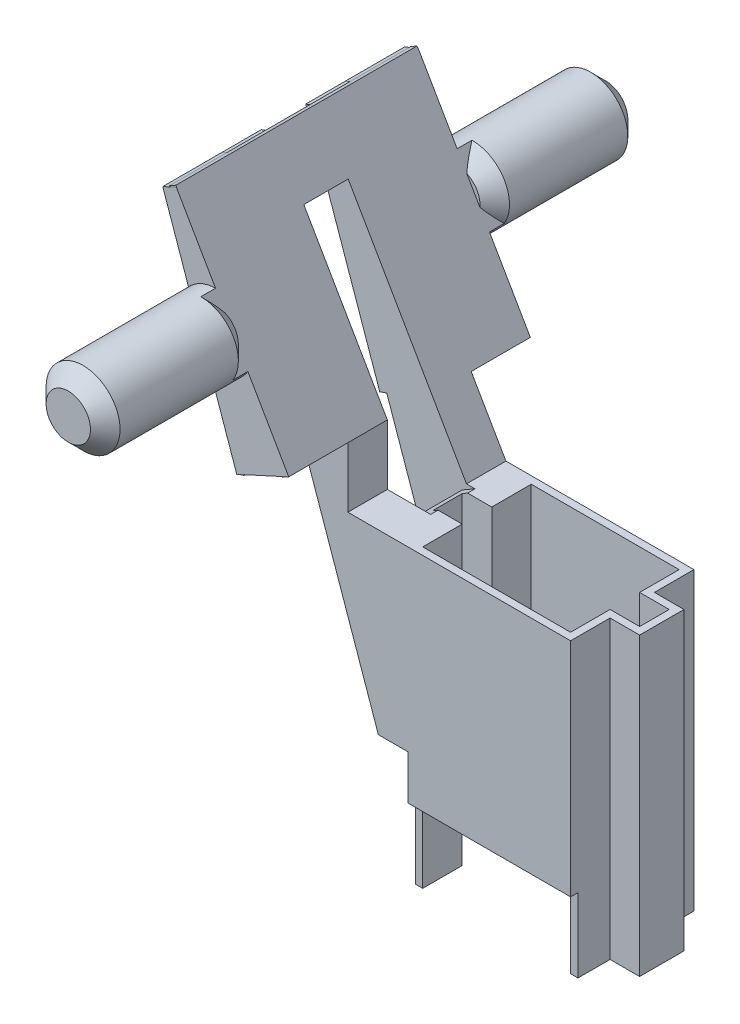
SolidWorks part; units mm, degrees
ref_plane "Ebene vorne" through (0, 0, 0) normal (0, 0, 1) x (1, 0, 0)
ref_plane "Ebene oben" through (0, 0, 0) normal (0, 1, 0) x (1, 0, 0)
ref_plane "Ebene rechts" through (0, 0, 0) normal (1, 0, 0) x (0, 0, -1)
sketch "Skizze1" plane through (0, 0, 0) normal (0, 1, 0) x (1, 0, 0)
  line L0 (-5, 1) -> (-5, 3.67)
  line L1 (5, -3.67) -> (-5, -3.67)
  line L2 (5, -3.67) -> (5, -1)
  line L3 (5, 3.67) -> (-5, 3.67)
  line L4 (-5, -3.67) -> (-5, -1)
  line L5 (5, -3.67) -> (-5, 3.67) construction
  line L6 (5, 3.67) -> (-5, -3.67) construction
  line L7 (7, -1) -> (5, -1)
  line L8 (7, -1) -> (7, 1)
  line L9 (7, 1) -> (5, 1)
  line L10 (-7, -1) -> (-7, 1)
  line L11 (7, -1) -> (-7, 1) construction
  line L12 (7, 1) -> (-7, -1) construction
  line L13 (5.5, -4.17) -> (-5.5, -4.17)
  line L14 (7.5, -1.5) -> (7.5, 1.5)
  line L15 (5.5, 4.17) -> (-5.5, 4.17)
  line L16 (-7.5, -1.5) -> (-7.5, 1.5)
  line L17 (5.5, -2.87) -> (-5.5, 2.87) construction
  line L18 (5.5, 3.21) -> (-5.5, -3.21) construction
  line L19 (-5, 1) -> (-7, 1)
  line L20 (5, 1) -> (5, 3.67)
  line L21 (-5, -1) -> (-7, -1)
  line L25 (-7.5, 1.5) -> (-5.5, 1.5)
  line L26 (-5.5, 4.17) -> (-5.5, 1.5)
  line L29 (7.5, 1.5) -> (5.5, 1.5)
  line L30 (5.5, 4.17) -> (5.5, 1.5)
  line L33 (7.5, -1.5) -> (5.5, -1.5)
  line L34 (5.5, -4.17) -> (5.5, -1.5)
  line L37 (-7.5, -1.5) -> (-5.5, -1.5)
  line L38 (-5.5, -4.17) -> (-5.5, -1.5)
  point P0 (0, 0)
  point P5 (0, 0)
  point P11 (0, 0)
  dimension "D1" = 10
  dimension "D2" = 2
  dimension "D3" = 14
  dimension "D4" = 0.5
  dimension "D5" = 0.5
  dimension "D6" = 7.34
  dimension "D7" = 0.5
  dimension "D8" = 0.5
  dimension "D9" = 0.5
  dimension "D10" = 0.5
  dimension "D11" = 0.5
  dimension "D12" = 0.5
extrude "Aufsatz-Linear austragen1" add sketch "Skizze1" along normal blind 20
sketch "Skizze8" plane through (0, 0, 3.67) normal (0, 0, -1) x (-1, 0, 0)
  line L0 (5.5, 20) -> (5.5, 0) construction
  line L1 (-5.5, 0) -> (5.5, 0)
  line L2 (-5.5, 0) -> (-5.5, 5)
  line L3 (-5.5, 5) -> (5.5, 5)
  line L4 (5.5, 0) -> (5.5, 5)
  dimension "D1" = 5
extrude "Schnitt-Linear austragen2" cut sketch "Skizze8" against normal up to next
sketch "Skizze10" plane through (0, 0, -4.17) normal (0, 0, -1) x (-1, 0, 0)
  line L1 (5.5, 20) -> (7.2113, 20)
  line L2 (5.5, 20) -> (5.5, 19.5)
  line L3 (5.5, 19.5) -> (7.5, 19.5)
  line L5 (7.5, 19.5) -> (17.6443, 37.0705)
  line L6 (17.6443, 37.0705) -> (17.2113, 37.3205)
  line L7 (17.2113, 37.3205) -> (7.2113, 20)
  line L8 (7.5, 20) -> (7.5, 0) construction
  dimension "D1" = 0.5
  dimension "D2" = 0.5
  dimension "D3" = 150
  dimension "D4" = 20
extrude "Aufsatz-Linear austragen3" add sketch "Skizze10" against normal up to vertex (8.34 mm away) up to point (-5.5, 20, 4.17)
sketch "Skizze12" plane through (0, 19.5, 0) normal (0, -1, 0) x (1, 0, 0)
  line L1 (-7, -1) -> (-5.5, -1)
  line L2 (-7, -1) -> (-7, 1)
  line L3 (-7, 1) -> (-5.5, 1)
  line L4 (-5.5, -1) -> (-5.5, 1)
extrude "Schnitt-Linear austragen3" cut sketch "Skizze12" against normal up to next
sketch "Skizze13" plane through (0, 0, -4.17) normal (0, 0, -1) x (-1, 0, 0)
  line L0 (17.2113, 37.3205) -> (9.5613, 24.0703)
  line L1 (17.2113, 37.3205) -> (7.2113, 20) construction
  line L2 (9.5613, 24.0703) -> (9.9943, 23.8203)
  line L3 (7.5, 19.5) -> (17.6443, 37.0705) construction
  line L4 (9.9943, 23.8203) -> (17.6443, 37.0705)
  line L5 (17.6443, 37.0705) -> (17.2113, 37.3205)
  dimension "D1" = 15.3
extrude "Aufsatz-Linear austragen4" add sketch "Skizze13" along normal blind 3.98
sketch "Skizze15" plane through (0, 0, -1.5) normal (0, 0, -1) x (-1, 0, 0)
  line L4 (5.5, 8) -> (5.5, 19.5)
  line L5 (5.5, 19.5) -> (7.5, 19.5)
  line L6 (7.5, 19.5) -> (17.6443, 37.0705)
  line L14 (17.6443, 37.0705) -> (7.5, 8)
  line L15 (7.5, 19.5) -> (7.5, 0) construction
  line L16 (7.5, 8) -> (5.5, 8)
  line L17 (5.5, 0) -> (7.5, 0) construction
  dimension "D1" = 8
extrude "Aufsatz-Linear austragen5" add sketch "Skizze15" along normal up to vertex (2.67 mm away) up to point (-7.5, 19.5, -4.17)
mirror "Spiegeln1" about plane through (0, 0, 0) normal (0, 0, 1) of "Aufsatz-Linear austragen4"
sketch "Skizze16" plane through (0, 0, 1.5) normal (0, 0, 1) x (1, 0, 0)
  line L0 (-17.6443, 37.0705) -> (-7.5, 8)
  line L1 (-7.5, 8) -> (-5.5, 8)
  line L2 (-5.5, 19.5) -> (-5.5, 5) construction
  line L3 (-5.5, 8) -> (-5.5, 19.5)
  line L4 (-5.5, 19.5) -> (-7.5, 19.5)
  line L5 (-7.5, 19.5) -> (-17.6443, 37.0705)
extrude "Aufsatz-Linear austragen6" add sketch "Skizze16" along normal up to vertex (2.67 mm away) up to point (-7.5, 19.5, 4.17)
sketch "Skizze17" plane through (2.8187, 1.6274, 0) normal (-0.866, -0.5, 0) x (0, 0, 1)
  line L0 (1.5, 40.9262) -> (1.5, 10.6782) construction
  line L1 (-1.5, 20.6375) -> (1.5, 20.6375)
  line L2 (-1.5, 20.6375) -> (-1.5, 36.9262)
  line L3 (-1.5, 36.9262) -> (1.5, 36.9262)
  line L4 (1.5, 20.6375) -> (1.5, 36.9262)
  line L6 (1.5, 40.9262) -> (-1.5, 40.9262) construction
  dimension "D1" = 4
extrude "Schnitt-Linear austragen4" cut sketch "Skizze17" against normal up to next
sketch "Skizze22" plane through (0, 0, -1.5) normal (0, 0, 1) x (1, 0, 0)
  line L0 (-17.6114, 36.9761) -> (-12.6034, 22.6248)
  line L1 (-17.6443, 37.0705) -> (-7.5, 8) construction
  line L2 (-12.6034, 22.6248) -> (-13.0755, 22.46)
  line L3 (-13.0755, 22.46) -> (-18.0835, 36.8114)
  line L4 (-18.0835, 36.8114) -> (-17.6114, 36.9761)
  dimension "D1" = 15.2
  dimension "D2" = 0.5
  dimension "D3" = 0.1
extrude "Aufsatz-Linear austragen15" add sketch "Skizze22" against normal blind 6.65
mirror "Spiegeln2" about plane through (0, 0, 0) normal (0, 0, 1) of "Aufsatz-Linear austragen15"
sketch "Skizze23" plane through (0, 0, 4.17) normal (0, 0, 1) x (1, 0, 0)
  line L0 (-7.2113, 20) -> (-9.5613, 20)
  line L1 (-9.5613, 20) -> (-9.5613, 24.0703)
  line L3 (-7.2113, 20) -> (-9.5613, 24.0703)
  line L4 (-9.5613, 24.0703) -> (-7.2113, 20) construction
extrude "Schnitt-Linear austragen5" cut sketch "Skizze23" against normal up to next
sketch "Skizze24" plane through (0, 0, 4.17) normal (0, 0, 1) x (1, 0, 0)
  line L2 (-17.6443, 37.0705) -> (-11.2989, 23.2225) construction
  line L3 (-18.0835, 36.8114) -> (-17.1613, 37.2339)
  line L4 (-18.0835, 36.8114) -> (-13.0755, 22.46) construction
  line L5 (-17.2113, 37.3205) -> (-9.5613, 24.0703) construction
  line L6 (-17.1613, 37.2339) -> (-9.5613, 24.0703)
  line L7 (-18.0835, 36.8114) -> (-13.0755, 22.46)
  line L8 (-13.0755, 22.46) -> (-9.5613, 24.0703)
  line L9 (-12.6034, 22.6248) -> (-9.9943, 23.8203) construction
  line L10 (-9.9943, 23.8203) -> (-17.6443, 37.0705) construction
  line L11 (-9.5613, 24.0703) -> (-9.9943, 23.8203) construction
  point P6 (0, 0)
  point P19 (0, 0)
  point P20 (0, 0)
  point P21 (-11.2989, 23.2225)
  point P22 (-18.0835, 36.8114)
  point P23 (0, 0)
  point P24 (-18.0181, 36.624)
  point P25 (0, 0)
  point P26 (0, 0)
  point P28 (0, 0)
extrude "Aufsatz-Linear austragen16" add sketch "Skizze24" along normal blind 4
sketch "Skizze25" plane through (0, 0, 8.17) normal (0, 0, 1) x (1, 0, 0)
  line L0 (-17.6224, 37.0226) -> (-11.3184, 23.2652) construction
  line L1 (-17.1613, 37.2339) -> (-18.0835, 36.8114) construction
  line L2 (-13.0755, 22.46) -> (-9.5613, 24.0703) construction
  circle A0 centre (-14.4704, 30.1439) radius 2.5
  dimension "D1" = 5
extrude "Aufsatz-Linear austragen17" add sketch "Skizze25" along normal blind 10
chamfer "Fase1" distance 1 angle 45 3 edges at (-11.9704, 30.1439, 18.17) (-16.8308, 29.3202, 8.17) (-12.3053, 31.3939, 8.17)
mirror "Spiegeln3" about plane through (0, 0, 0) normal (0, 0, 1) of "Fase1", "Aufsatz-Linear austragen16", "Aufsatz-Linear austragen17"
